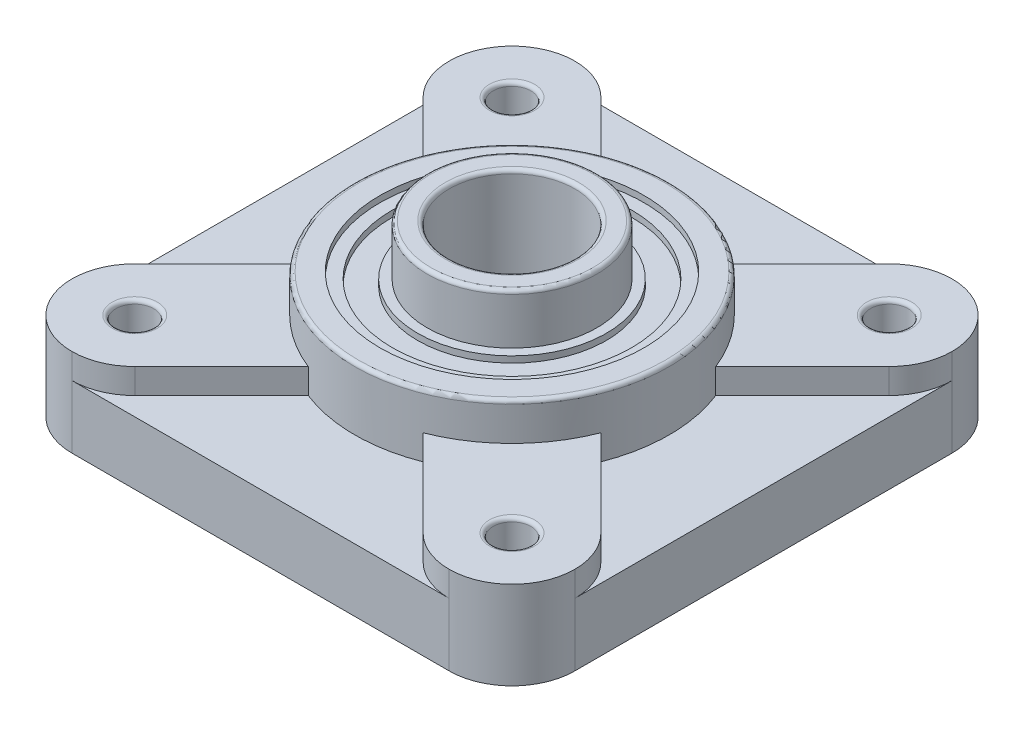
SolidWorks part; units mm, degrees
ref_plane "Front Plane" through (0, 0, 0) normal (0, 0, 1) x (1, 0, 0)
ref_plane "Top Plane" through (0, 0, 0) normal (0, 1, 0) x (1, 0, 0)
ref_plane "Right Plane" through (0, 0, 0) normal (1, 0, 0) x (0, 0, -1)
sketch "Sketch1" plane through (0, 0, 0) normal (0, 1, 0) x (1, 0, 0)
  line L1 (-15, -15) -> (15, -15) construction
  line L2 (-15, -15) -> (-15, 15) construction
  line L3 (-15, 15) -> (15, 15) construction
  line L4 (15, -15) -> (15, 15) construction
  line L5 (-15, -15) -> (15, 15) construction
  line L6 (-15, 15) -> (15, -15) construction
  line L7 (-20, -20) -> (20, -20)
  line L8 (-20, -20) -> (-20, 20)
  line L9 (-20, 20) -> (20, 20)
  line L10 (20, -20) -> (20, 20)
  line L11 (-20, -20) -> (20, 20) construction
  line L12 (-20, 20) -> (20, -20) construction
  circle A0 centre (-15, 15) radius 1.5
  circle A1 centre (15, 15) radius 1.5
  circle A2 centre (15, -15) radius 1.5
  circle A3 centre (-15, -15) radius 1.5
  point P0 (0, 0)
  point P7 (0, 0)
  point P21 (0, 0)
  dimension "D3" = 3
  dimension "D1" = 30
  dimension "D2" = 30
  dimension "D4" = 40
  dimension "D5" = 40
  dimension "D6" = 4
extrude "Boss-Extrude1" add sketch "Sketch1" along normal blind 5
fillet "Fillet1" radius 5 4 edges at (-20, 2.5, -20) (20, 2.5, -20) (-20, 2.5, 20) (20, 2.5, 20)
sketch "Sketch2" plane through (0, 5, 0) normal (0, 1, 0) x (1, 0, 0)
  circle A0 centre (0, 0) radius 12.5
  dimension "D1" = 25
extrude "Boss-Extrude2" add sketch "Sketch2" along normal blind 5
sketch "Sketch3" plane through (0, 10, 0) normal (0, 1, 0) x (1, 0, 0)
  circle A0 centre (0, 0) radius 10.5
  circle A1 centre (0, 0) radius 12.5 construction
  dimension "D1" = 2
extrude "Cut-Extrude1" cut sketch "Sketch3" against normal blind 0.5
sketch "Sketch4" plane through (0, 9.5, 0) normal (0, 1, 0) x (1, 0, 0)
  circle A0 centre (0, 0) radius 9.5
  circle A1 centre (0, 0) radius 7.5
  circle A2 centre (0, 0) radius 10.5 construction
  dimension "D1" = 1
  dimension "D2" = 2
extrude "Cut-Extrude2" cut sketch "Sketch4" against normal blind 0.5
sketch "Sketch5" plane through (0, 9.5, 0) normal (0, 1, 0) x (1, 0, 0)
  circle A0 centre (0, 0) radius 5
  circle A1 centre (0, 0) radius 6.75
  dimension "D1" = 10
  dimension "D2" = 1.75
extrude "Boss-Extrude3" add sketch "Sketch5" along normal blind 4
sketch "Sketch6" plane through (0, 9.5, 0) normal (0, 1, 0) x (1, 0, 0)
  circle A0 centre (0, 0) radius 5
extrude "Cut-Extrude3" cut sketch "Sketch6" against normal through all
sketch "Sketch7" plane through (0, 5, 0) normal (0, 1, 0) x (1, 0, 0)
  line L0 (11.6365, 4.5654) -> (20, 12.9289)
  line L1 (20, -15) -> (20, 15) construction
  line L2 (4.5654, 11.6365) -> (12.9289, 20)
  line L3 (15, 20) -> (-15, 20) construction
  line L4 (0, 0) -> (18.5355, 18.5355) construction
  line L5 (-20, 15) -> (-20, -15) construction
  line L6 (-15, -20) -> (15, -20) construction
  line L7 (-20, 15) -> (-20, -15)
  line L8 (-15, -20) -> (15, -20)
  line L9 (20, -15) -> (20, 15)
  line L10 (15, 20) -> (-15, 20)
  line L11 (11.6365, -4.5654) -> (20, -12.9289)
  line L12 (4.5654, -11.6365) -> (12.9289, -20)
  line L13 (-4.5654, -11.6365) -> (-12.9289, -20)
  line L14 (-11.6365, -4.5654) -> (-20, -12.9289)
  line L15 (-11.6365, 4.5654) -> (-20, 12.9289)
  line L16 (-4.5654, 11.6365) -> (-12.9289, 20)
  circle A0 centre (0, 0) radius 12.5 construction
  circle A1 centre (0, 0) radius 12.5 construction
  arc A2 (20, 15) -> (15, 20) centre (15, 15) ccw construction
  arc A3 (-15, 20) -> (-20, 15) centre (-15, 15) ccw construction
  arc A4 (-20, -15) -> (-15, -20) centre (-15, -15) ccw construction
  arc A5 (15, -20) -> (20, -15) centre (15, -15) ccw construction
  arc A6 (-15, 20) -> (-20, 15) centre (-15, 15) ccw
  arc A7 (-20, -15) -> (-15, -20) centre (-15, -15) ccw
  arc A8 (15, -20) -> (20, -15) centre (15, -15) ccw
  arc A9 (20, 15) -> (15, 20) centre (15, 15) ccw
  circle A10 centre (0, 0) radius 12.5
  circle A11 centre (15, -15) radius 1.5 construction
  circle A12 centre (-15, -15) radius 1.5 construction
  circle A13 centre (-15, 15) radius 1.5 construction
  circle A14 centre (15, 15) radius 1.5 construction
  circle A15 centre (15, -15) radius 1.5
  circle A16 centre (-15, -15) radius 1.5
  circle A17 centre (-15, 15) radius 1.5
  circle A18 centre (15, 15) radius 1.5
  point P51 (0, 0)
  circle M5 centre (0, 0) radius 12.5
  line M6 (15, 20) -> (-15, 20)
  arc M7 (-15, 20) -> (-20, 15) centre (-15, 15) ccw
  line M8 (-20, 15) -> (-20, -15)
  arc M9 (-20, -15) -> (-15, -20) centre (-15, -15) ccw
  line M10 (-15, -20) -> (15, -20)
  arc M11 (15, -20) -> (20, -15) centre (15, -15) ccw
  line M12 (20, -15) -> (20, 15)
  arc M13 (20, 15) -> (15, 20) centre (15, 15) ccw
  circle M14 centre (-15, 15) radius 1.5
  circle M15 centre (15, 15) radius 1.5
  circle M16 centre (15, -15) radius 1.5
  circle M17 centre (-15, -15) radius 1.5
  dimension "D1" = 10
  dimension "D2" = 5
  dimension "D3" = 4
extrude "Boss-Extrude4" add sketch "Sketch7" along normal blind 2 contours L16 L10 L15 M5 M7 M8 M14 | L4 A9 L2 M5 M15 M6 | L4 A10 L0 A18 M12 M13 | L12 L8 L11 M5 M11 M12 M16 | L14 L7 L13 M5 M9 M10 M17 region at (14.9404, 5, -11.3477) region at (11.3477, 5, -14.9404) region at (13.144, 5, 13.144) region at (-13.144, 5, -13.144) region at (-13.144, 5, 13.144)
fillet "Fillet2" radius 5 8 edges at (20, 6, -12.9289) (20, 6, 12.9289) (-12.9289, 6, -20) (12.9289, 6, -20) (-20, 6, 12.9289) (12.9289, 6, 20) (-12.9289, 6, 20) (-20, 6, -12.9289)
fillet "Fillet3" radius 0.3 4 edges at (15, 7, 16.5) (15, 7, -13.5) (-15, 7, -13.5) (-15, 7, 16.5)
fillet "Fillet4" radius 0.3 2 edges at (0, 10, 12.5) (0, 13.5, 5)
fillet "Fillet5" radius 0.3 1 edges at (0, 13.5, 6.75)
